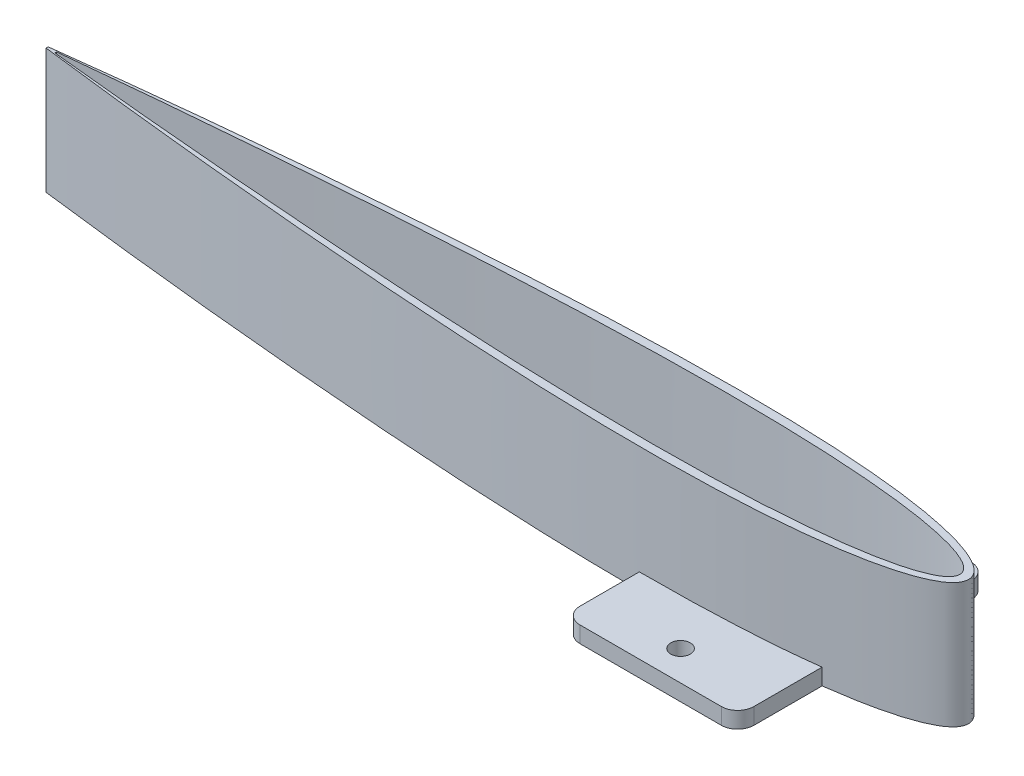
SolidWorks part; units mm, degrees
ref_plane "Front Plane" through (0, 0, 0) normal (0, 0, 1) x (1, 0, 0)
ref_plane "Top Plane" through (0, 0, 0) normal (0, 1, 0) x (1, 0, 0)
ref_plane "Right Plane" through (0, 0, 0) normal (1, 0, 0) x (0, 0, -1)
sketch "Sketch1" plane through (0, 0, 0) normal (0, 1, 0) x (1, 0, 0)
  line L0 (-167.983, 0.1908) -> (-167.983, -0.1908)
  spline S0 degree 3 poles (-167.983, 0.1908) (-167.8282, 0.2102) (-167.2106, 0.2875) (-165.8274, 0.4593) (-163.5389, 0.74) (-160.3701, 1.1209) (-156.3558, 1.5914) (-151.5399, 2.1387) (-145.9751, 2.7489) (-139.7225, 3.4072) (-132.8504, 4.0986) (-125.4343, 4.8075) (-117.5554, 5.5182) (-109.3001, 6.2139) (-100.7587, 6.8774) (-92.0248, 7.4902) (-83.194, 8.0329) (-74.3631, 8.4857) (-65.6287, 8.8291) (-57.0864, 9.0445) (-48.8296, 9.1159) (-40.9486, 9.0308) (-33.5298, 8.7816) (-26.654, 8.3656) (-20.3963, 7.7866) (-14.8244, 7.0533) (-9.9972, 6.1803) (-5.9657, 5.1838) (-2.7595, 4.0871) (-0.4062, 2.8938) (1.1586, 1.6049) (1.791, 0) (1.1586, -1.6049) (-0.4062, -2.8938) (-2.7595, -4.0871) (-5.9657, -5.1838) (-9.9972, -6.1803) (-14.8244, -7.0533) (-20.3963, -7.7866) (-26.654, -8.3656) (-33.5298, -8.7816) (-40.9486, -9.0308) (-48.8296, -9.1159) (-57.0864, -9.0445) (-65.6287, -8.8291) (-74.3631, -8.4857) (-83.194, -8.0329) (-92.0248, -7.4902) (-100.7587, -6.8774) (-109.3001, -6.2139) (-117.5554, -5.5182) (-125.4343, -4.8075) (-132.8504, -4.0986) (-139.7225, -3.4072) (-145.9751, -2.7489) (-151.5399, -2.1387) (-156.3558, -1.5914) (-160.3701, -1.1209) (-163.5389, -0.74) (-165.8274, -0.4593) (-167.2106, -0.2875) (-167.8282, -0.2102) (-167.983, -0.1908) knots 0 0 0 0 0.001358 0.005418 0.012134 0.02143 0.033203 0.04732 0.063625 0.081938 0.102054 0.123752 0.146793 0.170922 0.195874 0.221374 0.247142 0.272895 0.298352 0.323237 0.347281 0.370231 0.391843 0.411897 0.430189 0.446542 0.460807 0.472871 0.482671 0.490233 0.495774 0.5 0.504226 0.509767 0.517329 0.527129 0.539193 0.553458 0.569811 0.588103 0.608157 0.629769 0.652719 0.676763 0.701648 0.727105 0.752858 0.778626 0.804126 0.829078 0.853207 0.876248 0.897946 0.918062 0.936375 0.95268 0.966797 0.97857 0.987866 0.994582 0.998642 1 1 1 1
extrude "Boss-Extrude1" add sketch "Sketch1" along normal blind 23
sketch "Sketch2" plane through (0, 0, 0) normal (0, 1, 0) x (1, 0, 0)
  line L0 (-46.9, -23) -> (-20.9, -23)
  line L1 (-17.9, -20) -> (-17.9, 20)
  line L2 (-20.9, 23) -> (-46.9, 23)
  line L3 (-49.9, 20) -> (-49.9, -20)
  arc A0 (-20.9, -23) -> (-17.9, -20) centre (-20.9, -20) ccw
  arc A1 (-17.9, 20) -> (-20.9, 23) centre (-20.9, 20) ccw
  arc A2 (-46.9, 23) -> (-49.9, 20) centre (-46.9, 20) ccw
  arc A3 (-49.9, -20) -> (-46.9, -23) centre (-46.9, -20) ccw
extrude "Boss-Extrude2" add sketch "Sketch2" along normal blind 3
ref_plane "Plane1" through (0, 23, 0) normal (0, 1, 0) x (1, 0, 0)
sketch "Sketch3" plane through (0, 23, 0) normal (0, 1, 0) x (1, 0, 0)
  line L0 (-166.383, 0.1572) -> (-166.383, -0.1572)
  spline S0 degree 3 poles (-166.383, 0.1572) (-166.2311, 0.1732) (-165.6251, 0.2369) (-164.268, 0.3785) (-162.0226, 0.6097) (-158.9136, 0.9236) (-154.975, 1.3112) (-150.2498, 1.7622) (-144.79, 2.2649) (-138.6553, 2.8073) (-131.9129, 3.377) (-124.6367, 3.9611) (-116.9064, 4.5466) (-108.8068, 5.1199) (-100.4265, 5.6666) (-91.8574, 6.1714) (-83.1933, 6.6186) (-74.529, 6.9917) (-65.9596, 7.2745) (-57.5786, 7.452) (-49.478, 7.5108) (-41.7463, 7.4408) (-34.4682, 7.2354) (-27.7232, 6.8928) (-21.5849, 6.416) (-16.1202, 5.812) (-11.3869, 5.0939) (-7.4365, 4.273) (-4.2981, 3.3774) (-2.0052, 2.3941) (-0.4777, 1.3782) (0.1975, 0) (-0.4777, -1.3782) (-2.0052, -2.3941) (-4.2981, -3.3774) (-7.4365, -4.273) (-11.3869, -5.0939) (-16.1202, -5.812) (-21.5849, -6.416) (-27.7232, -6.8928) (-34.4682, -7.2354) (-41.7463, -7.4408) (-49.478, -7.5108) (-57.5786, -7.452) (-65.9596, -7.2745) (-74.529, -6.9917) (-83.1933, -6.6186) (-91.8574, -6.1714) (-100.4265, -5.6666) (-108.8068, -5.1199) (-116.9064, -4.5466) (-124.6367, -3.9611) (-131.9129, -3.377) (-138.6553, -2.8073) (-144.79, -2.2649) (-150.2498, -1.7622) (-154.975, -1.3112) (-158.9136, -0.9236) (-162.0226, -0.6097) (-164.268, -0.3785) (-165.6251, -0.2369) (-166.2311, -0.1732) (-166.383, -0.1572) knots 0 0 0 0 0.001361 0.005428 0.012156 0.02147 0.033267 0.047415 0.063758 0.082114 0.102282 0.124039 0.147146 0.171348 0.196379 0.221963 0.247821 0.273669 0.299223 0.324206 0.348349 0.37139 0.393087 0.41321 0.431552 0.447929 0.462182 0.474186 0.48386 0.491199 0.496361 0.5 0.503639 0.508801 0.51614 0.525814 0.537818 0.552071 0.568448 0.58679 0.606913 0.62861 0.651651 0.675794 0.700777 0.726331 0.752179 0.778037 0.803621 0.828652 0.852854 0.875961 0.897718 0.917886 0.936242 0.952585 0.966733 0.97853 0.987844 0.994572 0.998639 1 1 1 1
extrude "Cut-Extrude1" cut sketch "Sketch3" against normal blind 20
sketch "Sketch4" plane through (0, 0, 0) normal (0, 1, 0) x (1, 0, 0)
  circle A0 centre (-33.9, -17.5) radius 1.8
  circle A1 centre (-33.9, 17.5) radius 1.8
extrude "Cut-Extrude2" cut sketch "Sketch4" along normal blind 3
